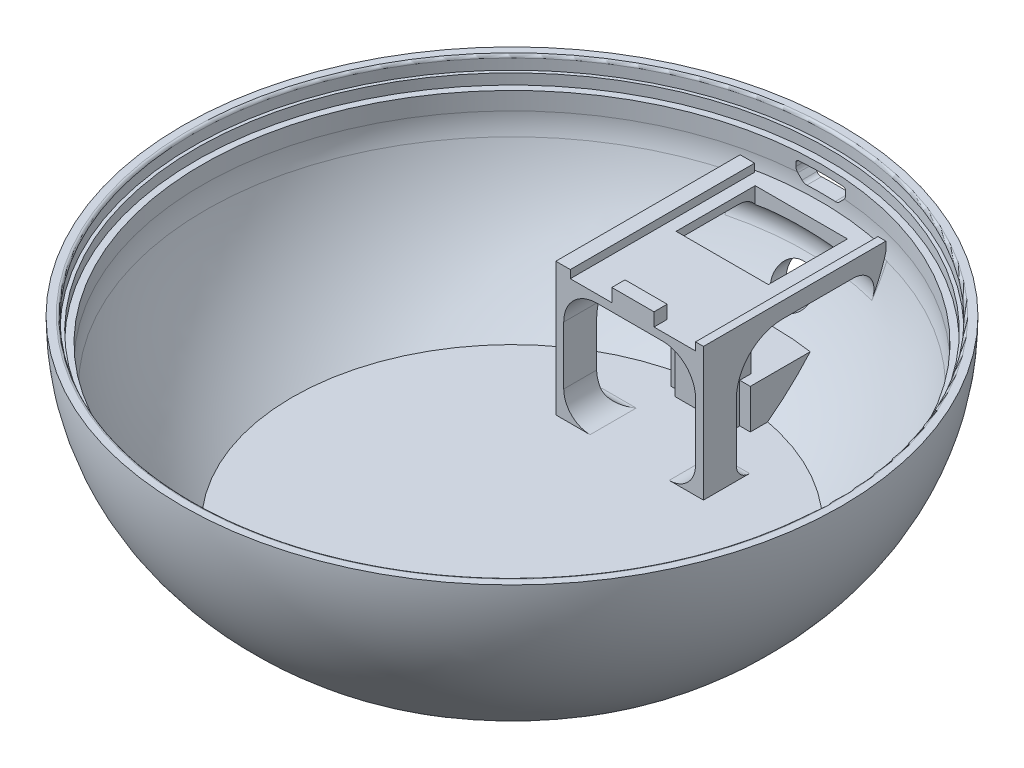
SolidWorks part; units mm, degrees
ref_plane "Plano frontal" through (0, 0, 0) normal (0, 0, 1) x (1, 0, 0)
ref_plane "Plano superior" through (0, 0, 0) normal (0, 1, 0) x (1, 0, 0)
ref_plane "Plano direito" through (0, 0, 0) normal (1, 0, 0) x (0, 0, -1)
sketch "Esboço1" plane through (0, 0, 0) normal (0, 0, 1) x (1, 0, 0)
  line L0 (0, 0) -> (0, -29.3333)
  line L1 (33.9935, -29.3333) -> (0, -29.3333)
  line L4 (0, 0) -> (50, 0)
  ellipse E0 centre (0, 0) end of major axis (-50, 0) minor radius 40 (33.9935, -29.3333) -> (50, 0) ccw
  dimension "D1" = 40
  dimension "D2" = 100
  dimension "D3" = 33.9935
revolve "Revolução1" add sketch "Esboço1" angle 360 about L0
shell "Casca1" thickness 2 removed face at (0, 0, 50)
sketch "Esboço7" plane through (0, 0, 0) normal (0, 1, 0) x (1, 0, 0)
  circle A0 centre (0, 0) radius 47
  circle A1 centre (0, 0) radius 48
  dimension "D1" = 94
extrude "Ressalto-extrusão3" add sketch "Esboço7" against normal up to next
sketch "Esboço9" plane through (0, 0, 0) normal (0, 1, 0) x (1, 0, 0)
  circle A0 centre (0, 0) radius 48.5
  dimension "D1" = 97
extrude "Corte-extrusão5" cut sketch "Esboço9" against normal blind 2
fillet "Filete3" radius 10 1 edges at (0, -7.7061, 47)
fillet "Filete4" radius 0.4 1 edges at (0, 0, 48.5)
fillet "Filete9" radius 6 1 edges at (0, -29.3333, 33.9935)
sketch "Esboço10" plane through (0, -2, 0) normal (0, 1, 0) x (1, 0, 0)
  circle A0 centre (0, 0) radius 48
  dimension "D1" = 96
extrude "Corte-extrusão6" cut sketch "Esboço10" against normal blind 1.6
sketch "Esboço15" plane through (0, 0, 0) normal (0, 0, 1) x (1, 0, 0)
  line L0 (0, -7.3333) -> (0, -4.7333) construction
  line L2 (-3.375, -4.7333) -> (3.375, -4.7333)
  line L3 (3.775, -5.1333) -> (3.775, -5.681)
  line L4 (3.4964, -6.3736) -> (2.8702, -7.0259)
  line L5 (2.1488, -7.3333) -> (-2.1488, -7.3333)
  line L6 (33.3248, -27.3333) -> (-33.3248, -27.3333) construction
  line L7 (-3.4964, -6.3736) -> (-2.8702, -7.0259)
  line L8 (-3.775, -5.1333) -> (-3.775, -5.681)
  arc A0 (2.8702, -7.0259) -> (2.1488, -7.3333) centre (2.1488, -6.3333) cw
  arc A1 (-2.8702, -7.0259) -> (-2.1488, -7.3333) centre (-2.1488, -6.3333) ccw
  arc A2 (3.775, -5.681) -> (3.4964, -6.3736) centre (2.775, -5.681) cw
  arc A3 (-3.4964, -6.3736) -> (-3.775, -5.681) centre (-2.775, -5.681) cw
  arc A4 (3.375, -4.7333) -> (3.775, -5.1333) centre (3.375, -5.1333) cw
  arc A5 (-3.775, -5.1333) -> (-3.375, -4.7333) centre (-3.375, -5.1333) cw
  point P14 (2.575, -7.3333)
  point P17 (-2.575, -7.3333)
  point P20 (3.775, -6.0833)
  point P23 (-3.775, -6.0833)
  point P26 (3.775, -4.7333)
  point P29 (-3.775, -4.7333)
  dimension "D6" = 1
  dimension "D7" = 0.4
  dimension "D1" = 7.55
  dimension "D2" = 2.6
  dimension "D3" = 1.35
  dimension "D4" = 5.15
  dimension "D5" = 20
extrude "Corte-extrusão9" cut sketch "Esboço15" against normal blind 62
ref_plane "Plano1" through (0, 0, -46.8482) normal (0, 0, -1) x (-1, 0, 0)
sketch "Esboço17" plane through (0, 0, -46.8482) normal (0, 0, -1) x (-1, 0, 0)
  line L0 (3.775, -5.681) -> (3.775, -5.1333) construction
  line L1 (11, -8.3333) -> (-11.4, -8.3333)
  line L2 (11, -8.3333) -> (11, -9.5333)
  line L3 (11, -9.5333) -> (-11.4, -9.5333)
  line L4 (-11.4, -8.3333) -> (-11.4, -9.5333)
  line L5 (-3.775, -5.1333) -> (-3.775, -5.681) construction
  line L7 (-3.375, -4.7333) -> (3.375, -4.7333) construction
  dimension "D1" = 1.2
  dimension "D2" = 7.225
  dimension "D3" = 22.4
  dimension "D4" = 3.6
  dimension "D5" = 7.625
extrude "Ressalto-extrusão4" add sketch "Esboço17" against normal blind 29.2
sketch "Esboço19" plane through (0, -9.5333, 0) normal (0, -1, 0) x (1, 0, 0)
  line L1 (-11, -17.6482) -> (-8.8, -17.6482)
  line L2 (-11, -17.6482) -> (-11, -45.6186)
  line L3 (-11, -45.6186) -> (-8.8, -45.6186)
  line L4 (-8.8, -17.6482) -> (-8.8, -45.6186)
  line L5 (11.4, -17.6482) -> (10.2, -17.6482)
  line L6 (11.4, -17.6482) -> (11.4, -45.3261)
  line L7 (11.4, -45.3261) -> (10.2, -45.3261)
  line L8 (10.2, -17.6482) -> (10.2, -45.3261)
  arc A0 (-11, -45.1386) -> (11.4, -45.0392) centre (0, 0) ccw construction
  dimension "D1" = 2.2
  dimension "D2" = 1.2
extrude "Ressalto-extrusão5" add sketch "Esboço19" against normal blind 2.4
sketch "Esboço20" plane through (0, -8.3333, 0) normal (0, 1, 0) x (1, 0, 0)
  line L0 (-8.8, 17.6482) -> (10.2, 17.6482) construction
  line L1 (-2.5, 17.6482) -> (3.9, 17.6482)
  line L2 (-2.5, 17.6482) -> (-2.5, 19.6482)
  line L3 (-2.5, 19.6482) -> (3.9, 19.6482)
  line L4 (3.9, 17.6482) -> (3.9, 19.6482)
  line L6 (-8.8, 17.6482) -> (-8.8, 45.6186) construction
  line L7 (10.2, 45.3261) -> (10.2, 17.6482) construction
  dimension "D1" = 2
  dimension "D2" = 6.3
  dimension "D3" = 6.4
  dimension "D4" = 6.3
extrude "Ressalto-extrusão6" add sketch "Esboço20" along normal blind 2
sketch "Esboço24" plane through (0, 0, 0) normal (0, 0, 1) x (1, 0, 0)
  line L1 (10.2, -27.3333) -> (11.4, -27.3333) construction
  ellipse E0 centre (0, -17.3333) end of major axis (-3, -17.3333) minor radius 2.5
  dimension "D1" = 10
  dimension "D2" = 6
  dimension "D3" = 2.5
extrude "Corte-extrusão12" cut sketch "Esboço24" against normal up to next
ref_plane "Plano2" through (0, -9.5333, 0) normal (0, -1, 0) x (-1, 0, 0)
sketch "Esboço29" plane through (0, -9.5333, 0) normal (0, -1, 0) x (-1, 0, 0)
  line L0 (0, 16.1333) -> (0, -16.1333) construction
  line L1 (4.4, 31.9) -> (-4.4, 31.9)
  line L2 (4.4, 31.9) -> (4.4, 29.1)
  line L3 (4.4, 29.1) -> (-4.4, 29.1)
  line L4 (-4.4, 31.9) -> (-4.4, 29.1)
  line L5 (4.4, 31.9) -> (-4.4, 29.1) construction
  line L6 (4.4, 29.1) -> (-4.4, 31.9) construction
  point P0 (0, 30.5)
  dimension "D3" = 30.5
  dimension "D1" = 8.8
  dimension "D2" = 2.8
extrude "Ressalto-extrusão11" add sketch "Esboço29" along normal up to surface and the other way up to next up to face at (0, -27.3333, 33.3248)
sketch "Esboço30" plane through (0, -8.3333, 0) normal (0, 1, 0) x (1, 0, 0)
  line L0 (0, -16.1333) -> (0, 16.1333) construction
  line L1 (-7, 43.9) -> (7, 43.9)
  line L2 (-7, 43.9) -> (-7, 31.9)
  line L3 (-7, 31.9) -> (7, 31.9)
  line L4 (7, 43.9) -> (7, 31.9)
  line L5 (-7, 43.9) -> (7, 31.9) construction
  line L6 (-7, 31.9) -> (7, 43.9) construction
  line L8 (-4.4, 31.9) -> (4.4, 31.9) construction
  point P0 (0, 37.9)
  dimension "D1" = 14
  dimension "D2" = 12
  dimension "D3" = 0
extrude "Corte-extrusão13" cut sketch "Esboço30" against normal blind 4
sketch "Esboço27" plane through (0, 0, 0) normal (1, 0, 0) x (0, 0, -1)
  line L0 (40.7485, -21.3333) -> (30.1545, -21.3333)
  line L1 (30.1545, -21.3333) -> (30.1545, -27.3333)
  line L2 (30.1545, -27.3333) -> (33.7166, -27.7767)
  line L4 (31.9, -27.3333) -> (29.1, -27.3333) construction
  line L5 (33.7166, -27.7767) -> (37.7706, -25.4136)
  line L6 (37.7706, -25.4136) -> (39.1733, -23.8825)
  line L7 (39.1733, -23.8825) -> (40.7485, -21.3333)
  line L8 (40.9291, -19.8333) -> (43.4209, -19.8333) construction
  dimension "D1" = 1.5
extrude "Ressalto-extrusão9" add sketch "Esboço27" along normal blind 6 and the other way blind 6
sketch "Esboço31" plane through (0, -9.5333, 0) normal (0, -1, 0) x (1, 0, 0)
  line L1 (-11, -17.6482) -> (-9.8, -17.6482)
  line L2 (-11, -17.6482) -> (-11, -22.6482)
  line L3 (-11, -22.6482) -> (-9.8, -22.6482)
  line L4 (-9.8, -17.6482) -> (-9.8, -22.6482)
  line L5 (11.4, -17.6482) -> (10.2, -17.6482)
  line L6 (11.4, -17.6482) -> (11.4, -22.6482)
  line L7 (11.4, -22.6482) -> (10.2, -22.6482)
  line L8 (10.2, -17.6482) -> (10.2, -22.6482)
  dimension "D1" = 1.2
  dimension "D2" = 5
  dimension "D3" = 5
  dimension "D4" = 1.2
extrude "Ressalto-extrusão12" add sketch "Esboço31" along normal up to next
fillet "Filete10" radius 7 2 edges at (10.8, -9.5333, -22.6482) (-10.4, -9.5333, -22.6482)
fillet "Filete11" radius 5 2 edges at (10.2, -9.5333, -23.6482) (-9.8, -9.5333, -23.6482)
fillet "Filete12" radius 4 2 edges at (10.2, -27.3333, -20.1482) (-9.8, -27.3333, -20.1482)
fillet "Filete13" radius 2 2 edges at (8.8, -27.3333, -22.6482) (-8.4, -27.3333, -22.6482)
fillet "Filete14" radius 3 1 edges at (0.2061, -9.5333, -46.4605)
